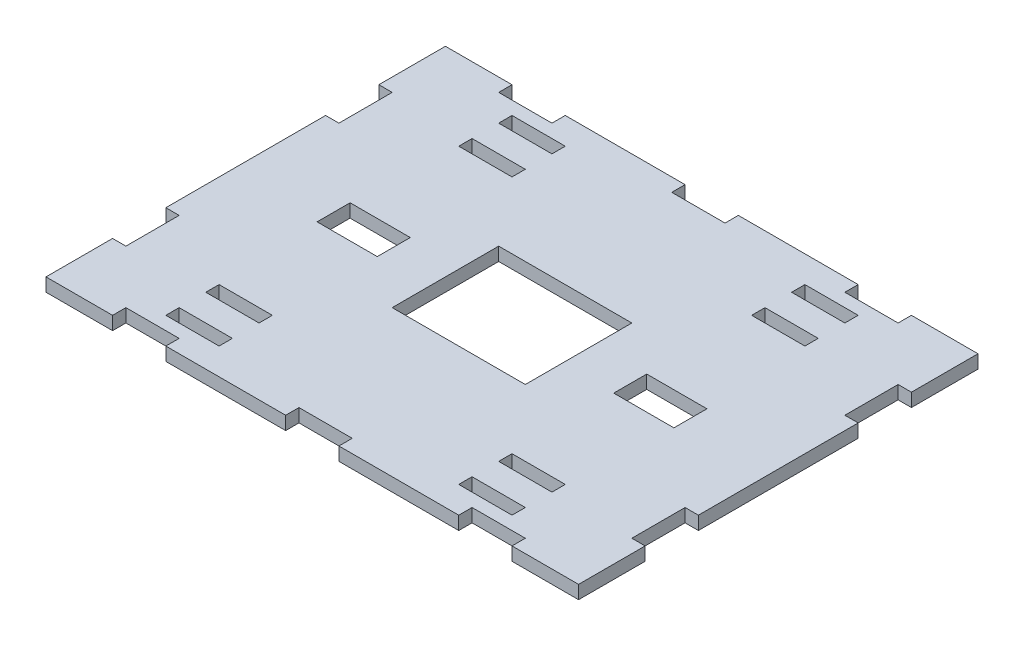
SolidWorks part; units mm, degrees
material "Very Low Density PE (SS)"
ref_plane "Front Plane" through (0, 0, 0) normal (0, 0, 1) x (1, 0, 0)
ref_plane "Top Plane" through (0, 0, 0) normal (0, 1, 0) x (1, 0, 0)
ref_plane "Right Plane" through (0, 0, 0) normal (1, 0, 0) x (0, 0, -1)
sketch "Sketch1" plane through (0, 0, 0) normal (0, 1, 0) x (1, 0, 0)
  line L0 (-125, 0) -> (125, 0) construction
  line L1 (-100, 75) -> (-75, 75)
  line L2 (-100, 75) -> (-100, 50)
  line L3 (-100, -75) -> (-75, -75)
  line L4 (100, 75) -> (100, 50)
  line L5 (0, 75) -> (0, -75) construction
  line L6 (-100, -55) -> (100, -55) construction
  line L11 (-65, -45) -> (-45, -45)
  line L12 (-65, -60) -> (-45, -60)
  line L25 (-65, -60) -> (-65, -65)
  line L26 (-25, 20) -> (25, 20)
  line L27 (-25, 20) -> (-25, -20)
  line L28 (-25, -20) -> (25, -20)
  line L29 (25, 20) -> (25, -20)
  line L30 (-25, 20) -> (25, -20) construction
  line L31 (-25, -20) -> (25, 20) construction
  line L32 (-65, -65) -> (-45, -65)
  line L33 (-45, -60) -> (-45, -65)
  line L34 (-45, -50) -> (-45, -45)
  line L35 (-65, -50) -> (-45, -50)
  line L36 (-65, -50) -> (-65, -45)
  line L37 (65, -65) -> (45, -65)
  line L38 (45, -60) -> (45, -65)
  line L39 (65, -60) -> (45, -60)
  line L40 (65, -60) -> (65, -65)
  line L41 (65, -50) -> (65, -45)
  line L42 (65, -50) -> (45, -50)
  line L43 (45, -50) -> (45, -45)
  line L44 (65, -45) -> (45, -45)
  line L45 (65, 50) -> (45, 50)
  line L46 (45, 50) -> (45, 45)
  line L47 (65, 45) -> (45, 45)
  line L48 (65, 50) -> (65, 45)
  line L49 (65, 60) -> (65, 65)
  line L50 (65, 60) -> (45, 60)
  line L51 (45, 60) -> (45, 65)
  line L52 (65, 65) -> (45, 65)
  line L53 (-65, 65) -> (-45, 65)
  line L54 (-45, 60) -> (-45, 65)
  line L55 (-65, 60) -> (-45, 60)
  line L56 (-65, 60) -> (-65, 65)
  line L57 (-65, 50) -> (-65, 45)
  line L58 (-65, 50) -> (-45, 50)
  line L59 (-45, 50) -> (-45, 45)
  line L60 (-65, 45) -> (-45, 45)
  line L61 (75, -70) -> (55, -70)
  line L63 (-75, -75) -> (-75, -70)
  line L64 (-75, -70) -> (-55, -70)
  line L65 (-55, -75) -> (-55, -70)
  line L66 (55, -75) -> (55, -70)
  line L68 (75, -75) -> (75, -70)
  line L69 (10, -75) -> (55, -75)
  line L70 (-10, -70) -> (10, -70)
  line L71 (-10, -70) -> (-10, -75)
  line L73 (10, -70) -> (10, -75)
  line L74 (-10, -70) -> (10, -75) construction
  line L75 (-10, -75) -> (10, -70) construction
  line L76 (-55, -75) -> (-10, -75)
  line L77 (75, -75) -> (100, -75)
  line L78 (75, 75) -> (75, 70)
  line L79 (55, 75) -> (55, 70)
  line L80 (75, 70) -> (55, 70)
  line L81 (10, 70) -> (10, 75)
  line L82 (-10, 70) -> (10, 70)
  line L83 (-10, 70) -> (-10, 75)
  line L84 (-55, 75) -> (-55, 70)
  line L85 (-75, 70) -> (-55, 70)
  line L86 (-75, 75) -> (-75, 70)
  line L87 (-10, 75) -> (0, 75) construction
  line L88 (10, 75) -> (55, 75)
  line L89 (0, 75) -> (10, 75) construction
  line L90 (-75, 75) -> (-55, 75) construction
  line L91 (-55, 75) -> (-10, 75)
  line L92 (55, 75) -> (75, 75) construction
  line L93 (75, 75) -> (100, 75)
  line L94 (100, -30) -> (95, -30)
  line L95 (100, 50) -> (95, 50)
  line L96 (100, 50) -> (100, 30) construction
  line L97 (100, 30) -> (95, 30)
  line L98 (95, 50) -> (95, 30)
  line L99 (95, -50) -> (95, -30)
  line L100 (100, -50) -> (95, -50)
  line L101 (100, -50) -> (100, -30) construction
  line L102 (100, 50) -> (100, 30) construction
  line L103 (100, 30) -> (100, -30)
  line L104 (100, -30) -> (100, -50) construction
  line L105 (100, -50) -> (100, -75)
  line L106 (-100, -30) -> (-95, -30)
  line L107 (-95, -50) -> (-95, -30)
  line L108 (-100, -50) -> (-95, -50)
  line L109 (-100, 30) -> (-95, 30)
  line L110 (-100, 50) -> (-95, 50)
  line L111 (-95, 50) -> (-95, 30)
  line L112 (-100, 50) -> (-100, 30) construction
  line L113 (-100, 30) -> (-100, -30)
  line L114 (-100, -30) -> (-100, -50) construction
  line L115 (-100, -50) -> (-100, -75)
  line L116 (67, -6.2) -> (44.4, -6.2)
  line L117 (-67, 6.2) -> (-44.4, 6.2)
  line L118 (-67, 6.2) -> (-67, -6.2)
  line L119 (-67, -6.2) -> (-44.4, -6.2)
  line L120 (-44.4, 6.2) -> (-44.4, -6.2)
  line L121 (-67, 6.2) -> (-44.4, -6.2) construction
  line L122 (-67, -6.2) -> (-44.4, 6.2) construction
  line L123 (44.4, 6.2) -> (44.4, -6.2)
  line L124 (67, 6.2) -> (44.4, 6.2)
  line L125 (67, 6.2) -> (67, -6.2)
  point P0 (0, 0)
  point P29 (0, 0)
  point P57 (0, -72.5)
  point P82 (-55.7, 0)
  dimension "D2" = 150
  dimension "D3" = 5
  dimension "D4" = 20
  dimension "D5" = 25
  dimension "D6" = 20
  dimension "D7" = 40
  dimension "D8" = 50
  dimension "D9" = 5
  dimension "D10" = 45
  dimension "D11" = 20
  dimension "D12" = 5
  dimension "D13" = 20
  dimension "D14" = 12.4
  dimension "D15" = 25
  dimension "D16" = 20
  dimension "D17" = 5
  dimension "D18" = 200
  dimension "D19" = 22.6
  dimension "D20" = 33
extrude "Boss-Extrude1" add sketch "Sketch1" along normal blind 5
